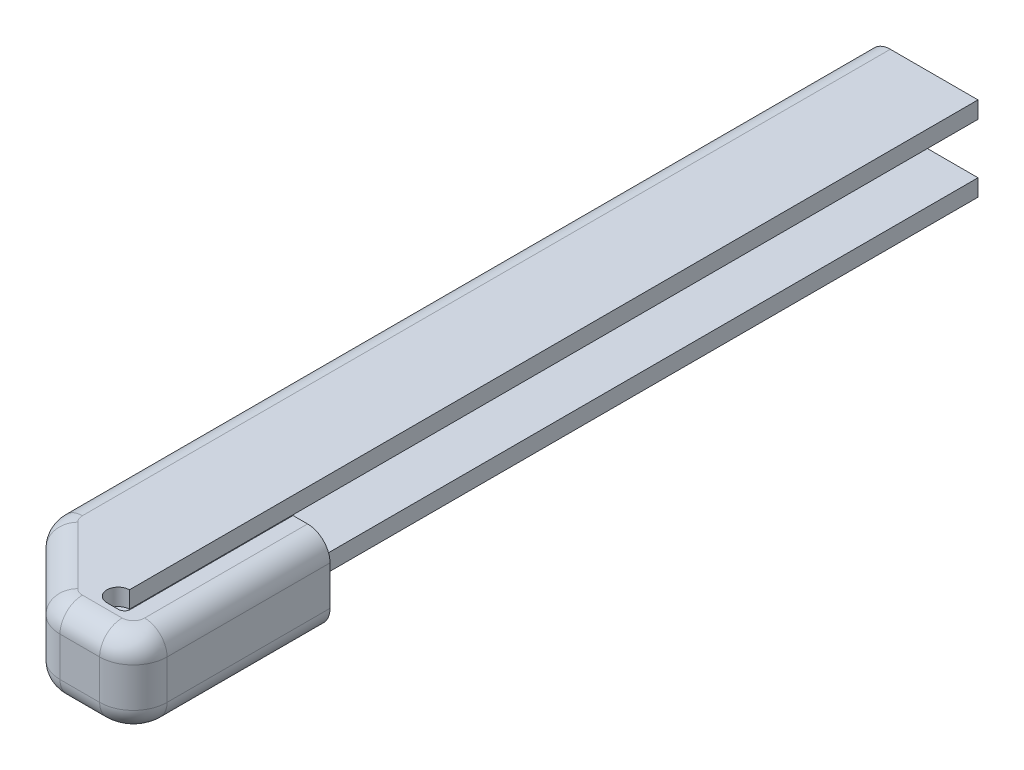
SolidWorks part; units mm, degrees
ref_plane "前视基准面" through (0, 0, 0) normal (0, 0, 1) x (1, 0, 0)
ref_plane "上视基准面" through (0, 0, 0) normal (0, 1, 0) x (1, 0, 0)
ref_plane "右视基准面" through (0, 0, 0) normal (1, 0, 0) x (0, 0, -1)
sketch "草图1" plane through (0, 0, 0) normal (0, 0, 1) x (1, 0, 0)
  line L1 (9.8, -7.5) -> (-9.8, -7.5)
  line L2 (9.8, -7.5) -> (9.8, 7.5)
  line L3 (9.8, 7.5) -> (-9.8, 7.5)
  line L4 (-9.8, -7.5) -> (-9.8, 7.5)
  line L5 (9.8, -7.5) -> (-9.8, 7.5) construction
  line L6 (9.8, 7.5) -> (-9.8, -7.5) construction
  point P0 (0, 0)
  dimension "D1" = 19.6
  dimension "D2" = 15
extrude "凸台-拉伸1" add sketch "草图1" along normal mid plane 155
sketch "草图2" plane through (0, 0, 77.5) normal (0, 0, 1) x (1, 0, 0)
  line L0 (9.8, -7.5) -> (9.8, 7.5) construction
  line L1 (12.9154, 7.5) -> (19.5, 7.5)
  line L2 (19.5, 7.5) -> (19.5, -7.5)
  line L3 (19.5, -7.5) -> (12.9154, -7.5)
  line L4 (-9.8, -7.5) -> (9.8, -7.5) construction
  line L5 (-9.8, 7.5) -> (-9.8, -7.5) construction
  arc A0 (12.9154, 7.5) -> (12.9154, -7.5) centre (27.5, 0) ccw
  dimension "D1" = 17.7
  dimension "D2" = 32.8
  dimension "D3" = 29.3
extrude "凸台-拉伸2" add sketch "草图2" against normal blind 30 separate body
sketch "草图3" plane through (0, 0, 77.5) normal (0, 0, 1) x (1, 0, 0)
  line L1 (19.5, -7.5) -> (-9.8, -7.5)
  line L2 (19.5, -7.5) -> (19.5, 7.5)
  line L3 (19.5, 7.5) -> (-9.8, 7.5)
  line L4 (-9.8, -7.5) -> (-9.8, 7.5)
  line L5 (19.5, -7.5) -> (-9.8, 7.5) construction
  line L6 (19.5, 7.5) -> (-9.8, -7.5) construction
  point P0 (4.85, 0)
extrude "凸台-拉伸3" add sketch "草图3" along normal blind 5
sketch "草图4" plane through (0, 0, -77.5) normal (0, 0, -1) x (-1, 0, 0)
  line L0 (-9.8, -7.5) -> (-9.8, 7.5) construction
  line L1 (6.8, -4.5) -> (-9.8, -4.5)
  line L2 (6.8, -4.5) -> (6.8, 4.5)
  line L3 (6.8, 4.5) -> (-9.8, 4.5)
  line L4 (-9.8, -4.5) -> (-9.8, 4.5)
  line L5 (6.8, -4.5) -> (-9.8, 4.5) construction
  line L6 (6.8, 4.5) -> (-9.8, -4.5) construction
  line L7 (-9.8, 7.5) -> (9.8, 7.5) construction
  line L8 (9.8, 7.5) -> (9.8, -7.5) construction
  point P0 (-1.5, 0)
  dimension "D1" = 3
  dimension "D2" = 3
extrude "切除-拉伸1" cut sketch "草图4" against normal up to surface (155 mm away) up to face at (10.9039, 0, 77.5)
fillet "圆角1" radius 1 1 edges at (11.1, 0, 77.5)
chamfer "倒角1" distance 10 angle 45 1 edges at (-6.8, 0, 77.5)
sketch "草图5" plane through (0, 7.5, 0) normal (0, 1, 0) x (1, 0, 0)
  line L0 (-9.8, -68.7426) -> (3.9574, -82.5)
  line L1 (-9.8, -82.5) -> (-9.8, 77.5) construction
  line L2 (19.5, -82.5) -> (-9.8, -82.5) construction
  line L3 (-9.8, -68.7426) -> (-9.8, -82.5)
  line L4 (-9.8, -82.5) -> (3.9574, -82.5)
  line L5 (3.2, -77.5) -> (-6.8, -67.5) construction
  line L6 (3.2, -77.5) -> (-6.8, -67.5) construction
  dimension "D1" = 3
extrude "切除-拉伸2" cut sketch "草图5" against normal through all
sketch "草图6" plane through (0, 7.5, 0) normal (0, 1, 0) x (1, 0, 0)
  line L0 (9.8, -77.5) -> (9.8, 77.5) construction
  circle A0 centre (9.8, -75.5) radius 2
  dimension "D1" = 4
extrude "切除-拉伸3" cut sketch "草图6" against normal through all
fillet "圆角2" radius 6 1 edges at (19.5, 0, 82.5)
fillet "圆角3" radius 3 2 edges at (-6.8, 0, 67.5) (3.2, 0, 77.5)
fillet "圆角4" radius 6 2 edges at (3.9574, 0, 82.5) (-9.8, 0, 68.7426)
fillet "圆角5" radius 1 10 edges at (7.1213, 4.5, 77.5) (3.2946, 4.5, 77.2716) (-1.8, 4.5, 72.5) (-6.5716, 4.5, 67.4054) (-6.8, -4.5, -5.6213) (-6.5716, -4.5, 67.4054) (7.1213, -4.5, 77.5) (3.2946, -4.5, 77.2716) (-6.8, 4.5, -5.6213) (-1.8, -4.5, 72.5)
fillet "圆角6" radius 4 14 edges at (-9.8, -7.5, -5.6213) (-9.3433, -7.5, 68.5535) (-2.9213, -7.5, 75.6213) (4.1465, -7.5, 82.0433) (19.5, -7.5, 62) (17.7426, -7.5, 80.7426) (19.5, 7.5, 62) (17.7426, 7.5, 80.7426) (-9.8, 7.5, -5.6213) (-9.3433, 7.5, 68.5535) (-2.9213, 7.5, 75.6213) (4.1465, 7.5, 82.0433) (9.9713, -7.5, 82.5) (9.9713, 7.5, 82.5)
